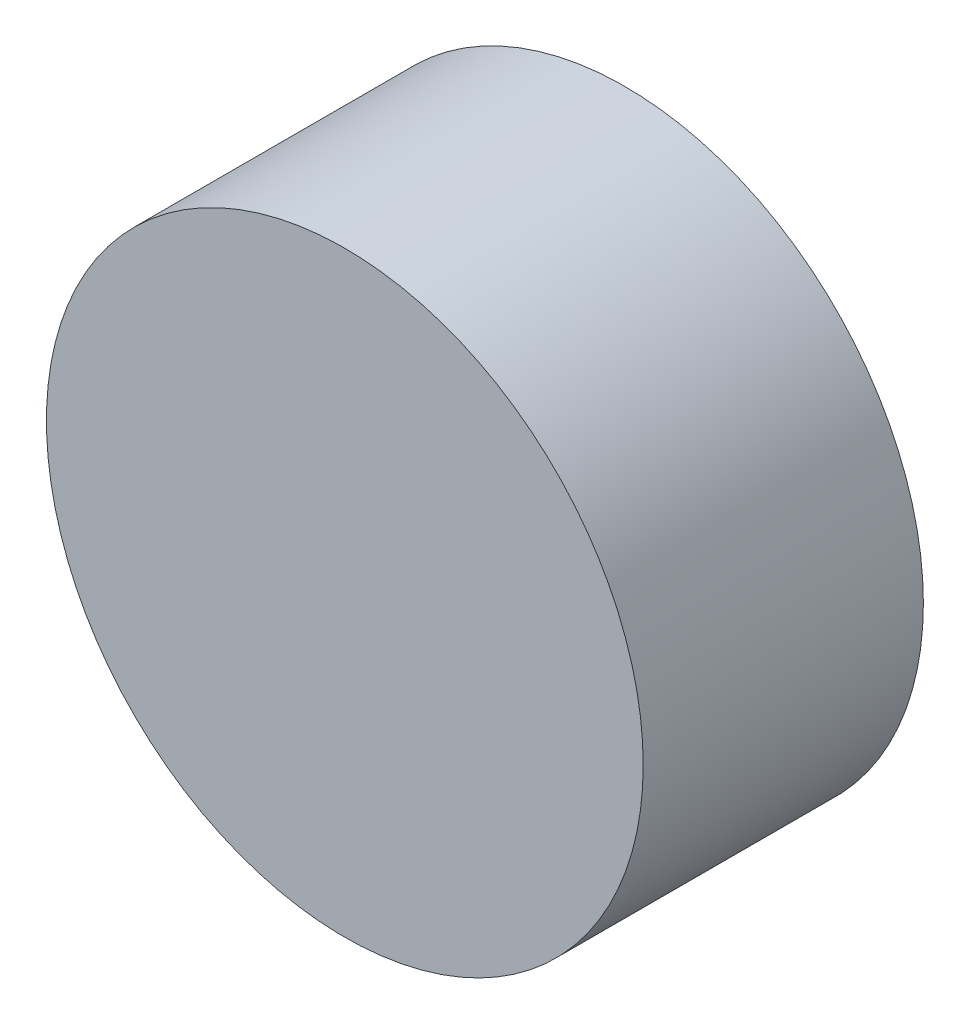
SolidWorks part; units mm, degrees
ref_plane "Front Plane" through (0, 0, 0) normal (0, 0, 1) x (1, 0, 0)
ref_plane "Top Plane" through (0, 0, 0) normal (0, 1, 0) x (1, 0, 0)
ref_plane "Right Plane" through (0, 0, 0) normal (1, 0, 0) x (0, 0, -1)
sketch "Sketch1" plane through (0, 0, 0) normal (0, 0, 1) x (1, 0, 0)
  line L0 (0, 0) -> (0, 45) construction
  line L1 (0, 0) -> (17.6777, 17.6777) construction
  circle A0 centre (0, 0) radius 45
  circle A1 centre (0, 0) radius 31.5
  circle A2 centre (0, 0) radius 25 construction
  circle A3 centre (0, 0) radius 15.75
  circle A4 centre (17.6777, 17.6777) radius 2.5
  circle A5 centre (0, 25) radius 3
  circle A6 centre (17.6777, -17.6777) radius 2.5
  circle A7 centre (-17.6777, -17.6777) radius 2.5
  circle A8 centre (-17.6777, 17.6777) radius 2.5
  point P20 (0, 0)
  dimension "D1" = 90
  dimension "D2" = 63
  dimension "D3" = 50
  dimension "D4" = 31.5
  dimension "D5" = 5
  dimension "D7" = 6
  dimension "D6" = 45
  dimension "D8" = 4
extrude "Boss-Extrude1" add sketch "Sketch1" along normal blind 48.75 contours A0
extrude "Cut-Extrude1" cut sketch "Sketch1<3>" along normal blind 6.5 contours A0 A1 region at (-43.7272, 0, 0)
sketch "Sketch1<3>" plane through (0, 0, 0) normal (0, 0, 1) x (1, 0, 0) same geometry as "Sketch1"
extrude "Cut-Extrude2" cut sketch "Sketch1<4>" along normal blind 6.2 contours A3 | A8 | A4 | A6 | A7 region at (0, 0, 0) region at (17.6777, 17.6777, 0) region at (17.6777, -17.6777, 0) region at (-17.6777, -17.6777, 0) region at (-17.6777, 17.6777, 0)
sketch "Sketch1<4>" plane through (0, 0, 0) normal (0, 0, 1) x (1, 0, 0) same geometry as "Sketch1"
equation "\"M6 Screw\"= 5mm"
equation "\"Flange to Part A\"= 90mm"
equation "\"Part A to Part b\"= 120mm"
equation "\"Part B to Part C\"= 120"
